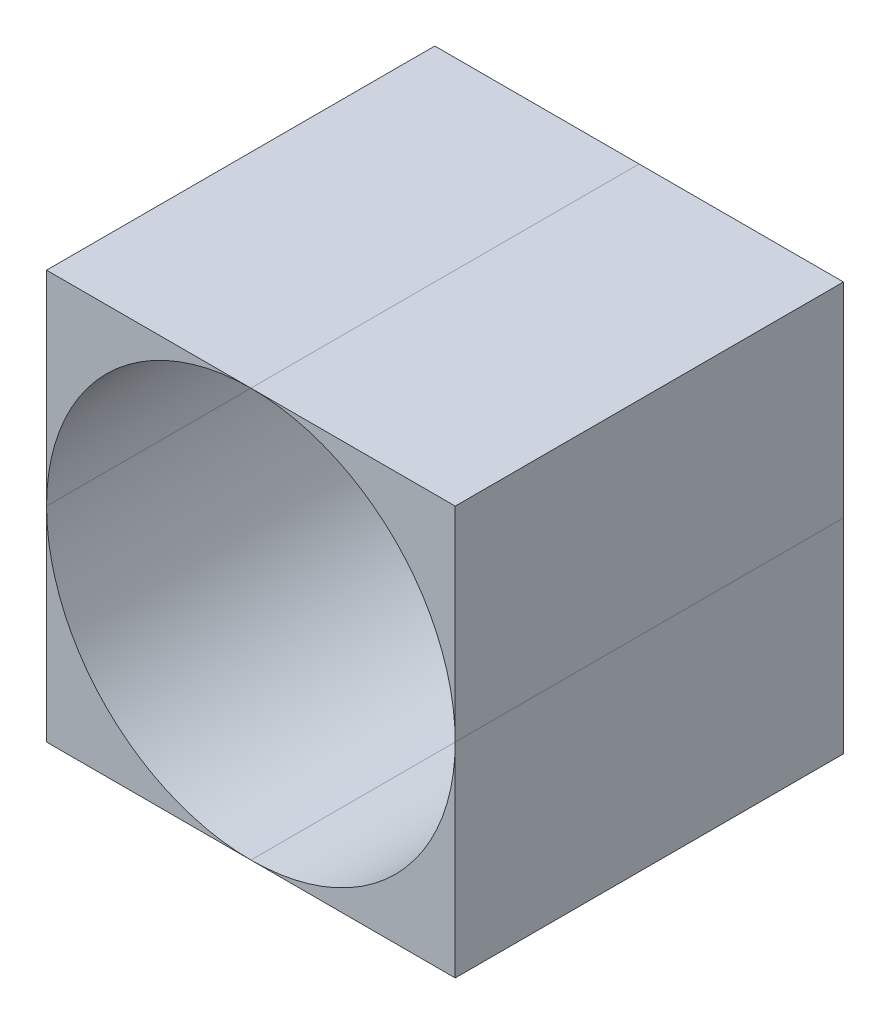
SolidWorks part; units mm, degrees
ref_plane "Front Plane" through (0, 0, 0) normal (0, 0, 1) x (1, 0, 0)
ref_plane "Top Plane" through (0, 0, 0) normal (0, 1, 0) x (1, 0, 0)
ref_plane "Right Plane" through (0, 0, 0) normal (1, 0, 0) x (0, 0, -1)
sketch "Sketch1" plane through (0, 0, 0) normal (0, 0, 1) x (1, 0, 0)
  line L1 (-5, -5) -> (5, -5)
  line L2 (-5, -5) -> (-5, 5)
  line L3 (-5, 5) -> (5, 5)
  line L4 (5, -5) -> (5, 5)
  line L5 (-5, -5) -> (5, 5) construction
  line L6 (-5, 5) -> (5, -5) construction
  circle A0 centre (0, 0) radius 5
  dimension "D1" = 10
extrude "Boss-Extrude1" add sketch "Sketch1" along normal blind 9.5 contours A0 L4 L3 | A0 L1 L4 | A0 L2 L1 | A0 L3 L2 region at (-3.8832, -3.8832, 0) region at (3.8832, -3.8832, 0) region at (-3.8832, 3.8832, 0) region at (3.8832, 3.8832, 0)
